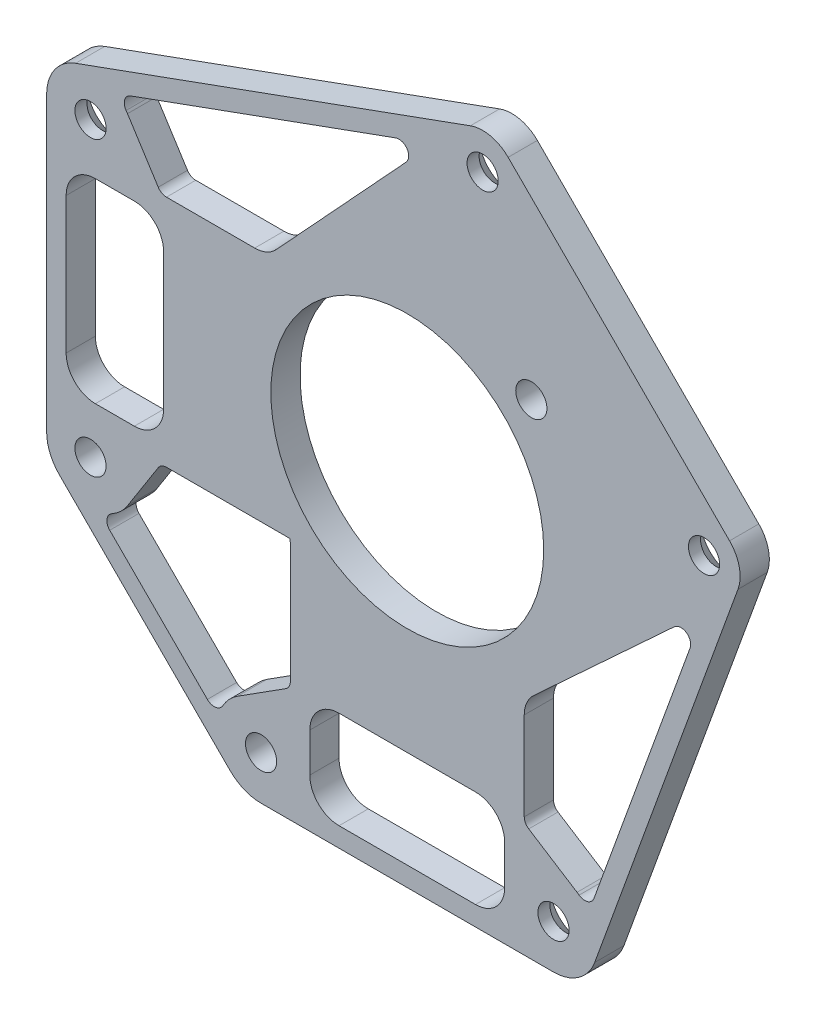
SolidWorks part; units mm, degrees
material "6061-T6 (SS)"
ref_plane "Front Plane" through (0, 0, 0) normal (0, 0, 1) x (1, 0, 0)
ref_plane "Top Plane" through (0, 0, 0) normal (0, 1, 0) x (1, 0, 0)
ref_plane "Right Plane" through (0, 0, 0) normal (1, 0, 0) x (0, 0, -1)
sketch "Sketch1" plane through (0, 0, 0) normal (0, 0, 1) x (1, 0, 0)
  line L0 (-7.7139, 20.2317) -> (-27.0698, -0.7279)
  line L1 (-2.3793, 20.3378) -> (20.3378, -2.3793)
  line L2 (0, 0) -> (-12.7279, -12.7279) construction
  line L8 (-49.7279, -19.7279) -> (-49.7279, -5.7279)
  line L9 (-44.7279, -22.7279) -> (-40.7279, -22.7279)
  line L10 (-47.7279, -19.7279) -> (-47.7279, -5.7279)
  line L11 (-44.7279, -2.7279) -> (-40.7279, -2.7279)
  line L12 (-37.7279, -19.7279) -> (-37.7279, -5.7279)
  line L13 (-47.7279, -22.7279) -> (-37.7279, -2.7279) construction
  line L14 (-47.7279, -2.7279) -> (-37.7279, -22.7279) construction
  line L19 (-44.7279, -0.7279) -> (-40.7279, -0.7279)
  line L21 (-44.7279, -24.7279) -> (-40.7279, -24.7279)
  line L22 (-40.7279, -0.7279) -> (-27.0698, -0.7279)
  line L23 (-40.7279, -24.7279) -> (-24.7695, -24.7279)
  line L24 (20.2317, -7.7139) -> (-0.7279, -27.0698)
  line L25 (-35.7279, -19.7279) -> (-35.7279, -5.7279) construction
  line L26 (-24.7279, -40.7279) -> (-24.7279, -24.7695)
  line L27 (-0.7279, -40.7279) -> (-0.7279, -27.0698)
  line L28 (-2.7279, -47.7279) -> (-22.7279, -37.7279) construction
  line L29 (-22.7279, -47.7279) -> (-2.7279, -37.7279) construction
  line L30 (-24.7279, -44.7279) -> (-24.7279, -40.7279)
  line L31 (-0.7279, -44.7279) -> (-0.7279, -40.7279)
  line L32 (-19.7279, -37.7279) -> (-5.7279, -37.7279)
  line L33 (-2.7279, -44.7279) -> (-2.7279, -40.7279)
  line L34 (-19.7279, -47.7279) -> (-5.7279, -47.7279)
  line L35 (-22.7279, -44.7279) -> (-22.7279, -40.7279)
  line L36 (-19.7279, -49.7279) -> (-5.7279, -49.7279)
  arc A0 (-3.7936, 16.5194) -> (-6.1977, 18.9236) centre (-4.9956, 17.7215) ccw construction
  arc A1 (-6.1977, 18.9236) -> (-3.7936, 16.5194) centre (-4.9956, 17.7215) ccw construction
  arc A2 (-3.7936, 16.5194) -> (-6.1977, 18.9236) centre (-4.9956, 17.7215) ccw construction
  arc A3 (-6.1977, 18.9236) -> (-3.7936, 16.5194) centre (-4.9956, 17.7215) ccw construction
  circle A8 centre (-12.7279, -12.7279) radius 12.7 construction
  circle A9 centre (-12.7279, -12.7279) radius 12.7 construction
  circle A10 centre (-12.7279, -12.7279) radius 14
  arc A11 (-2.3793, 20.3378) -> (-7.7139, 20.2317) centre (-4.9956, 17.7215) ccw
  arc A13 (-24.7695, -24.7279) -> (-24.7279, -24.7695) centre (-12.7279, -12.7279) ccw
  arc A14 (-44.7279, -22.7279) -> (-47.7279, -19.7279) centre (-44.7279, -19.7279) cw
  arc A15 (-40.7279, -22.7279) -> (-37.7279, -19.7279) centre (-40.7279, -19.7279) ccw
  arc A16 (-40.7279, -2.7279) -> (-37.7279, -5.7279) centre (-40.7279, -5.7279) cw
  arc A17 (-47.7279, -5.7279) -> (-44.7279, -2.7279) centre (-44.7279, -5.7279) cw
  arc A18 (-49.7279, -5.7279) -> (-44.7279, -0.7279) centre (-44.7279, -5.7279) cw
  arc A21 (-44.7279, -24.7279) -> (-49.7279, -19.7279) centre (-44.7279, -19.7279) cw
  arc A22 (-40.7279, -24.7279) -> (-35.7279, -19.7279) centre (-40.7279, -19.7279) ccw construction
  arc A23 (-40.7279, -0.7279) -> (-35.7279, -5.7279) centre (-40.7279, -5.7279) cw construction
  arc A24 (-24.7279, -44.7279) -> (-19.7279, -49.7279) centre (-19.7279, -44.7279) ccw
  arc A25 (-5.7279, -49.7279) -> (-0.7279, -44.7279) centre (-5.7279, -44.7279) ccw
  arc A26 (-5.7279, -47.7279) -> (-2.7279, -44.7279) centre (-5.7279, -44.7279) ccw
  arc A27 (-2.7279, -40.7279) -> (-5.7279, -37.7279) centre (-5.7279, -40.7279) ccw
  arc A28 (-22.7279, -40.7279) -> (-19.7279, -37.7279) centre (-19.7279, -40.7279) cw
  arc A29 (-22.7279, -44.7279) -> (-19.7279, -47.7279) centre (-19.7279, -44.7279) ccw
  arc A30 (16.5194, -3.7936) -> (18.9236, -6.1977) centre (17.7215, -4.9956) cw construction
  arc A31 (18.9236, -6.1977) -> (16.5194, -3.7936) centre (17.7215, -4.9956) cw construction
  arc A32 (20.3378, -2.3793) -> (20.2317, -7.7139) centre (17.7215, -4.9956) cw
  point P0 (-42.7279, -12.7279)
  point P42 (0, 0)
  point P63 (-12.7279, -42.7279)
  point P83 (8.9792, 8.9792)
  dimension "D2" = 28
  dimension "D3" = 2
  dimension "D4" = 3
  dimension "D5" = 18.7
  dimension "D9" = 3
  dimension "D6" = 30
  dimension "D7" = 10
  dimension "D8" = 20
  dimension "D10" = 2
extrude "Boss-Extrude1" add sketch "Sketch1" along normal blind 3
fillet "Fillet1" radius 3 3 edges at (-0.7279, -27.0698, 1.5) (-24.7279, -24.7695, 1.5) (-27.0698, -0.7279, 1.5)
hole_wizard "M3 Clearance Hole1" positions "Sketch2" profile "Sketch3" hole size "M3" standard "ANSI Metric" end condition up to next
sketch "Sketch2" plane through (0, 0, 0) normal (0, 0, -1) x (-1, 0, 0)
  point P7 (0, 0)
sketch "Sketch3" plane through (0, 0, 0) normal (1, 0, 0) x (0, 1, 0)
  line L0 (0, 0) -> (0, 3)
  line L1 (0, 3) -> (1.6, 3)
  line L2 (1.6, 3) -> (1.6, 0)
  line L5 (1.6, 0) -> (0, 0)
  line L11 (0, -6.35) -> (0, 107.95) construction
  dimension "Thru Hole Dia." = 3.2
  dimension "Thru Hole Depth" = 3
hole_wizard "CSK for M3 SFHCS1" positions "Sketch4" profile "Sketch5" countersink size "M3" standard "ANSI Metric" end condition up to next
sketch "Sketch4" plane through (0, 0, 0) normal (0, 0, -1) x (-1, 0, 0)
  point P3 (4.9956, 17.7215)
  point P8 (-17.7215, -4.9956)
sketch "Sketch5" plane through (-4.9956, 17.7215, 0) normal (1, 0, 0) x (0, 1, 0)
  line L0 (0, 0) -> (0, 3)
  line L1 (0, 3) -> (1.6, 3)
  line L2 (1.6, 3) -> (1.6, 1.76)
  line L3 (1.6, 1.76) -> (3.36, 0)
  line L5 (3.36, 0) -> (0, 0)
  line L6 (-1.6, 1.76) -> (-3.36, 0) construction
  line L11 (0, -6.35) -> (0, 107.95) construction
  dimension "Thru Hole Dia." = 3.2
  dimension "Thru Hole Depth" = 3
  dimension "Near C'Sink Dia." = 6.72
  dimension "Near C'Sink Angle" = 90
sketch "Sketch8" plane through (0, 0, 3) normal (0, 0, 1) x (1, 0, 0)
  line L0 (-45.2279, -12.7279) -> (-45.2279, 2.2721) construction
  line L1 (-49.7279, -19.7279) -> (-49.7279, -5.7279) construction
  line L2 (-44.7279, -2.7279) -> (-40.7279, -2.7279) construction
  line L3 (-49.7279, 2.2721) -> (-49.7279, -5.7279)
  line L7 (-45.2279, -12.7279) -> (-42.7279, -12.7279) construction
  line L10 (-41.4318, 4.6886) -> (-37.9837, -0.7279)
  line L12 (-42.7279, -12.7279) -> (-42.7279, -2.7279) construction
  line L13 (-40.7279, -0.7279) -> (-27.0698, -0.7279) construction
  line L14 (-44.7279, -0.7279) -> (-37.9837, -0.7279)
  line L15 (-41.4318, -30.1445) -> (-37.9837, -24.7279)
  line L16 (-44.7279, -24.7279) -> (-37.9837, -24.7279)
  line L17 (-49.7279, -27.7279) -> (-49.7279, -19.7279)
  arc A0 (-41.4318, 4.6886) -> (-49.7279, 2.2721) centre (-45.2279, 2.2721) ccw
  arc A3 (-44.7279, -0.7279) -> (-49.7279, -5.7279) centre (-44.7279, -5.7279) ccw construction
  arc A4 (-44.7279, -0.7279) -> (-49.7279, -5.7279) centre (-44.7279, -5.7279) ccw
  arc A7 (-40.7279, -0.7279) -> (-35.7279, -5.7279) centre (-40.7279, -5.7279) cw construction
  arc A8 (-44.7279, -24.7279) -> (-49.7279, -19.7279) centre (-44.7279, -19.7279) cw
  arc A9 (-41.4318, -30.1445) -> (-49.7279, -27.7279) centre (-45.2279, -27.7279) cw
  dimension "D2" = 9
  dimension "D1" = 5
extrude "Boss-Extrude3" add sketch "Sketch8" against normal up to surface (3 mm away) up to face at (-8.3556, 17.7215, 0)
hole_wizard "CSK for M3 SFHCS2" positions "Sketch9" profile "Sketch10" countersink size "M3" standard "ANSI Metric" end condition up to next
sketch "Sketch9" plane through (0, 0, 0) normal (0, 0, -1) x (-1, 0, 0)
  point P0 (45.2279, 2.2721)
sketch "Sketch10" plane through (-45.2279, 2.2721, 0) normal (1, 0, 0) x (0, 1, 0)
  line L0 (0, 0) -> (0, 3)
  line L1 (0, 3) -> (1.6, 3)
  line L2 (1.6, 3) -> (1.6, 1.76)
  line L3 (1.6, 1.76) -> (3.36, 0)
  line L5 (3.36, 0) -> (0, 0)
  line L6 (-1.6, 1.76) -> (-3.36, 0) construction
  line L11 (0, -6.35) -> (0, 107.95) construction
  dimension "Thru Hole Dia." = 3.2
  dimension "Thru Hole Depth" = 3
  dimension "Near C'Sink Dia." = 6.72
  dimension "Near C'Sink Angle" = 90
hole_wizard "M3 Clearance Hole2" positions "Sketch11" profile "Sketch12" hole size "M3" standard "ANSI Metric" end condition up to next
sketch "Sketch11" plane through (0, 0, 0) normal (0, 0, -1) x (-1, 0, 0)
  point P0 (45.2279, -27.7279)
sketch "Sketch12" plane through (-45.2279, -27.7279, 0) normal (1, 0, 0) x (0, 1, 0)
  line L0 (0, 0) -> (0, 3)
  line L1 (0, 3) -> (1.6, 3)
  line L2 (1.6, 3) -> (1.6, 0)
  line L5 (1.6, 0) -> (0, 0)
  line L11 (0, -6.35) -> (0, 107.95) construction
  dimension "Thru Hole Dia." = 3.2
  dimension "Thru Hole Depth" = 3
ref_plane "Plane1" through (0, 0, 0) normal (-0.7071, 0.7071, 0) x (0.7071, 0.7071, 0)
mirror "Mirror1" about plane through (0, 0, 0) normal (-0.7071, 0.7071, 0) of "M3 Clearance Hole2", "CSK for M3 SFHCS2", "Boss-Extrude3"
sketch "Sketch13" plane through (0, 0, 0) normal (0, 0, -1) x (-1, 0, 0)
  line L0 (-21.1996, -6.2577) -> (-6.5022, -46.7628)
  line L1 (-0.2367, -26.179) -> (-20.2317, -7.7139) construction
  line L2 (-17.6929, -10.0584) -> (-20.2317, -7.7139)
  line L3 (-17.6929, -10.0584) -> (-5.8984, -42.5634)
  line L4 (38.8909, -38.8909) -> (-38.8909, 38.8909) construction
  line L5 (10.0584, 17.6929) -> (7.7139, 20.2317)
  line L6 (6.2577, 21.1996) -> (46.7628, 6.5022)
  line L7 (10.0584, 17.6929) -> (42.5634, 5.8984)
  line L8 (30.9099, -48.4099) -> (48.4099, -30.9099)
  line L9 (32.1414, -44.3499) -> (44.3499, -32.1414)
  arc A0 (-20.3378, -2.3793) -> (-20.2317, -7.7139) centre (-17.7215, -4.9956) ccw construction
  arc A1 (-4.6886, -41.4318) -> (-2.2721, -49.7279) centre (-2.2721, -45.2279) ccw construction
  arc A2 (-21.1996, -6.2577) -> (-20.2317, -7.7139) centre (-17.7215, -4.9956) ccw
  arc A3 (-5.8984, -42.5634) -> (-6.5022, -46.7628) centre (-2.2721, -45.2279) ccw
  arc A4 (6.2577, 21.1996) -> (7.7139, 20.2317) centre (4.9956, 17.7215) cw
  arc A5 (42.5634, 5.8984) -> (46.7628, 6.5022) centre (45.2279, 2.2721) cw
  arc A6 (27.7279, -49.7279) -> (30.1445, -41.4318) centre (27.7279, -45.2279) ccw construction
  arc A7 (41.4318, -30.1445) -> (49.7279, -27.7279) centre (45.2279, -27.7279) ccw construction
  arc A8 (44.3499, -32.1414) -> (48.4099, -30.9099) centre (45.2279, -27.7279) ccw
  arc A9 (30.9099, -48.4099) -> (32.1414, -44.3499) centre (27.7279, -45.2279) ccw
  dimension "D1" = 2
  dimension "D2" = 2
extrude "Boss-Extrude4" add sketch "Sketch13" against normal up to surface (3 mm away) up to face at (-29.3279, -45.2279, 3)
fillet "Fillet2" radius 1 10 edges at (-32.1414, -44.3499, 1.5) (-24.7279, -37.9837, 1.5) (-37.9837, -24.7279, 1.5) (-44.3499, -32.1414, 1.5) (5.8984, -42.5634, 1.5) (-0.7279, -37.9837, 1.5) (-42.5634, 5.8984, 1.5) (-37.9837, -0.7279, 1.5) (-10.0584, 17.6929, 1.5) (17.6929, -10.0584, 1.5)
